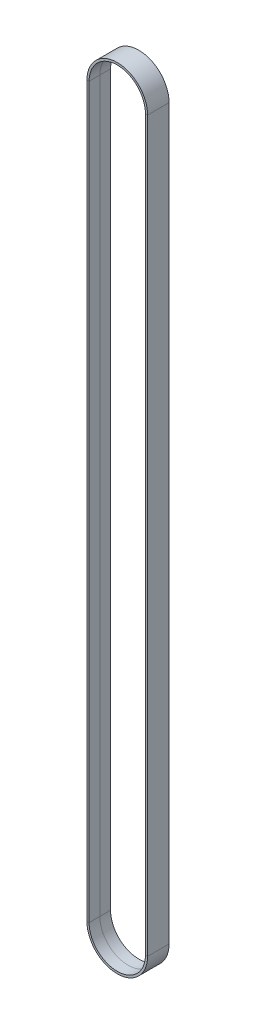
SolidWorks part; units mm, degrees
ref_plane "Спереди" through (0, 0, 0) normal (0, 0, 1) x (1, 0, 0)
ref_plane "Сверху" through (0, 0, 0) normal (0, 1, 0) x (1, 0, 0)
ref_plane "Справа" through (0, 0, 0) normal (1, 0, 0) x (0, 0, -1)
sketch "Эскиз2" plane through (0, 0, 0) normal (0, 0, 1) x (1, 0, 0)
  line L0 (0, 0) -> (1, 0) construction
  line L1 (0, 0) -> (0, 1) construction
  line L2 (26.25, 0) -> (26.25, -678.6787)
  line L3 (-26.25, -678.6787) -> (-26.25, 0)
  arc A0 (-26.25, 0) -> (26.25, 0) centre (0, 0) cw
  arc A1 (26.25, -678.6787) -> (-26.25, -678.6787) centre (0, -678.6787) cw
ref_plane "Плоскость1" through (0, 0, 0) normal (0, 0, 1) x (1, 0, 0)
sketch "Эскиз3" plane through (0, 0, 0) normal (0, 0, 1) x (1, 0, 0)
  line L0 (-26.25, -678.6787) -> (-26.25, 0) construction
  line L1 (26.25, 0) -> (26.25, -678.6787) construction
  line L2 (-26.25, -678.6787) -> (-26.25, 0)
  line L3 (26.25, 0) -> (26.25, -678.6787)
  arc A0 (-26.25, -678.6787) -> (26.25, -678.6787) centre (0, -678.6787) ccw construction
  arc A1 (26.25, 0) -> (-26.25, 0) centre (0, 0) ccw construction
  arc A2 (-26.25, -678.6787) -> (26.25, -678.6787) centre (0, -678.6787) ccw
  arc A3 (26.25, 0) -> (-26.25, 0) centre (0, 0) ccw
ref_plane "Плоскость2" through (0, 0, 0) normal (0, 1, 0) x (1, 0, 0)
sketch "Эскиз4" plane through (0, 0, 0) normal (0, 1, 0) x (1, 0, 0)
  line L2 (26.25, 0) -> (26.25, -10)
  line L3 (26.25, -10) -> (28.25, -10)
  line L6 (26.25, 0) -> (26.25, 10)
  line L7 (26.25, 10) -> (28.25, 10)
  line L10 (18.6383, -10) -> (15.4502, -10) construction
  line L11 (18.3632, 10) -> (21.7997, 10) construction
  line L12 (28.25, -10) -> (28.25, 10)
  dimension "D1" = 2
  dimension "D2" = 2
sweep "По траектории1" add profiles "Эскиз4" path "Эскиз3"
